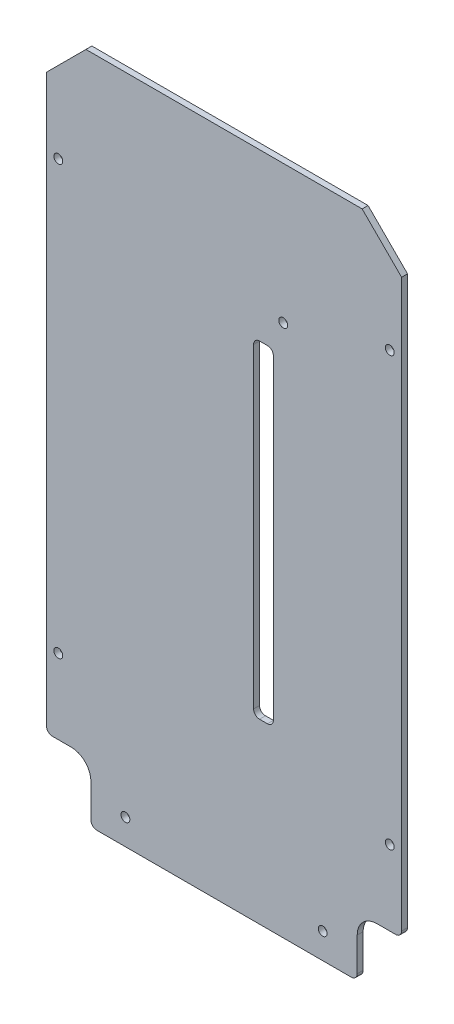
SolidWorks part; units mm, degrees
ref_plane "Plan de face" through (0, 0, 0) normal (0, 0, 1) x (1, 0, 0)
ref_plane "Plan de dessus" through (0, 0, 0) normal (0, 1, 0) x (1, 0, 0)
ref_plane "Plan de droite" through (0, 0, 0) normal (1, 0, 0) x (0, 0, -1)
sketch "Esquisse1" plane through (0, 0, 0) normal (0, 0, 1) x (1, 0, 0)
  line L1 (0, 0) -> (180, 0)
  line L2 (0, 0) -> (0, 340)
  line L3 (0, 340) -> (180, 340)
  line L4 (180, 0) -> (180, 340)
  dimension "D1" = 180
  dimension "D2" = 340
extrude "Boss.-Extru.1" add sketch "Esquisse1" along normal blind 3
sketch "Esquisse2" plane through (0, 0, 3) normal (0, 0, 1) x (1, 0, 0)
  line L0 (0, 13) -> (180, 13) construction
  line L1 (0, 340) -> (0, 0) construction
  line L2 (180, 0) -> (180, 340) construction
  line L3 (0, 0) -> (180, 0) construction
  circle A0 centre (40, 13) radius 2.25
  circle A1 centre (140, 13) radius 2.25
  dimension "D1" = 4.5
  dimension "D3" = 40
  dimension "D4" = 100
  dimension "D2" = 13
extrude "Enlèv. mat.-Extru.1" cut sketch "Esquisse2" against normal through all both and the other way through all
sketch "Esquisse3" plane through (0, 0, 3) normal (0, 0, 1) x (1, 0, 0)
  line L1 (0, 0) -> (22.5, 0)
  line L2 (0, 0) -> (0, 30)
  line L3 (0, 30) -> (22.5, 30)
  line L4 (22.5, 0) -> (22.5, 30)
  line L5 (180, 0) -> (157.5, 0)
  line L6 (180, 0) -> (180, 30)
  line L7 (180, 30) -> (157.5, 30)
  line L8 (157.5, 0) -> (157.5, 30)
  dimension "D1" = 30
  dimension "D2" = 22.5
  dimension "D3" = 22.5
extrude "Enlèv. mat.-Extru.2" cut sketch "Esquisse3" against normal through all both and the other way through all
fillet "Congé1" radius 10 2 edges at (157.5, 30, 1.5) (22.5, 30, 1.5)
fillet "Congé2" radius 3 4 edges at (0, 30, 1.5) (22.5, 0, 1.5) (180, 30, 1.5) (157.5, 0, 1.5)
sketch "Esquisse4" plane through (0, 0, 3) normal (0, 0, 1) x (1, 0, 0)
  line L0 (0, 340) -> (0, 33) construction
  line L1 (105, 256) -> (115, 256)
  line L2 (105, 256) -> (105, 90)
  line L3 (105, 90) -> (115, 90)
  line L4 (115, 256) -> (115, 90)
  line L5 (25.5, 0) -> (154.5, 0) construction
  dimension "D1" = 105
  dimension "D2" = 10
  dimension "D3" = 90
  dimension "D4" = 166
extrude "Enlèv. mat.-Extru.3" cut sketch "Esquisse4" against normal through all both and the other way through all
fillet "Congé3" radius 3 4 edges at (105, 256, 1.5) (115, 256, 1.5) (115, 90, 1.5) (105, 90, 1.5)
chamfer "Chanfrein1" distance 20 angle 45 1 edges at (180, 340, 1.5)
chamfer "Chanfrein2" distance 20 angle 45 1 edges at (0, 340, 1.5)
sketch "Esquisse5" plane through (0, 0, 3) normal (0, 0, 1) x (1, 0, 0)
  line L0 (180, 270) -> (120, 270) construction
  line L1 (180, 33) -> (180, 320) construction
  line L2 (25.5, 0) -> (154.5, 0) construction
  circle A0 centre (120, 270) radius 2.25
  dimension "D2" = 4.5
  dimension "D1" = 60
  dimension "D3" = 270
extrude "Enlèv. mat.-Extru.4" cut sketch "Esquisse5" against normal through all
sketch "Esquisse6" plane through (0, 0, 3) normal (0, 0, 1) x (1, 0, 0)
  line L0 (6, 0) -> (6, 285) construction
  line L1 (0, 320) -> (0, 33) construction
  line L2 (6, 0) -> (0, 0) construction
  line L3 (0, 176.5) -> (180, 176.5) construction
  line L4 (180, 33) -> (180, 320) construction
  line L5 (90, 176.5) -> (90, -87.4402) construction
  circle A0 centre (6, 285) radius 2.25
  circle A1 centre (6, 68) radius 2.25
  circle A2 centre (174, 68) radius 2.25
  circle A3 centre (174, 285) radius 2.25
  dimension "D1" = 4.5
  dimension "D4" = 68
  dimension "D2" = 285
  dimension "D3" = 6
extrude "Enlèv. mat.-Extru.5" cut sketch "Esquisse6" against normal through all both and the other way through all
